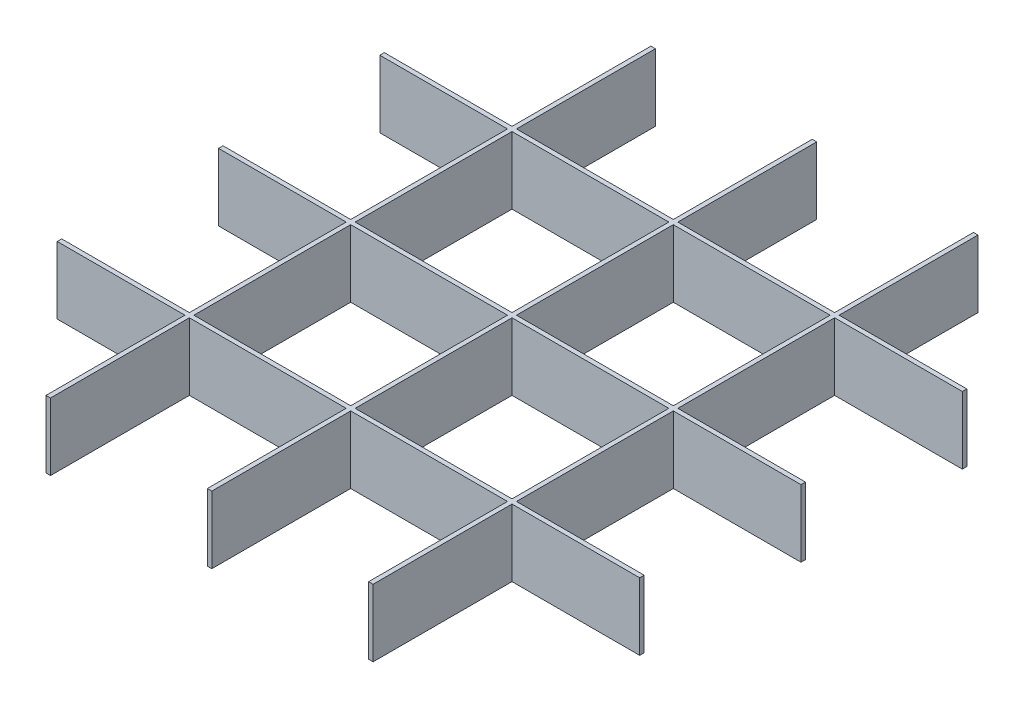
SolidWorks part; units mm, degrees
ref_plane "前视基准面" through (0, 0, 0) normal (0, 0, 1) x (1, 0, 0)
ref_plane "上视基准面" through (0, 0, 0) normal (0, 1, 0) x (1, 0, 0)
ref_plane "右视基准面" through (0, 0, 0) normal (1, 0, 0) x (0, 0, -1)
other "Configuration Table"
sketch "草图1" plane through (0, 0, 0) normal (0, 1, 0) x (1, 0, 0)
  line L0 (-130, 0) -> (130, 0) construction
  line L1 (130, -135) -> (-130, -135) construction
  line L2 (130, -135) -> (130, 135) construction
  line L3 (130, 135) -> (-130, 135) construction
  line L4 (-130, -135) -> (-130, 135) construction
  line L5 (130, -135) -> (-130, 135) construction
  line L6 (130, 135) -> (-130, -135) construction
  line L7 (0, 135) -> (0, -135) construction
  line L8 (-71, 73) -> (-1, 73)
  line L9 (-130, 73) -> (-73, 73)
  line L10 (-130, 73) -> (-130, 71)
  line L11 (-130, 71) -> (-73, 71)
  line L12 (130, 73) -> (130, 71)
  line L13 (-130, 1) -> (-73, 1)
  line L14 (-130, 1) -> (-130, -1)
  line L15 (-130, -1) -> (-73, -1)
  line L16 (130, 1) -> (130, -1)
  line L17 (-130, -71) -> (-73, -71)
  line L18 (-130, -71) -> (-130, -73)
  line L19 (-130, -73) -> (-73, -73)
  line L20 (130, -71) -> (130, -73)
  line L21 (-73, 135) -> (-71, 135)
  line L22 (-73, 135) -> (-73, 73)
  line L23 (-73, -135) -> (-71, -135)
  line L24 (-71, 135) -> (-71, 73)
  line L25 (-1, 135) -> (1, 135)
  line L26 (-1, 135) -> (-1, 73)
  line L27 (-1, -135) -> (1, -135)
  line L28 (1, 135) -> (1, 73)
  line L29 (71, 135) -> (73, 135)
  line L30 (71, 135) -> (71, 73)
  line L31 (71, -135) -> (73, -135)
  line L32 (73, 135) -> (73, 73)
  line L33 (-71, 71) -> (-1, 71)
  line L34 (-71, 71) -> (-71, 1)
  line L35 (-73, 71) -> (-73, 1)
  line L36 (-71, 1) -> (-1, 1)
  line L37 (-71, -1) -> (-71, -71)
  line L38 (-73, -1) -> (-73, -71)
  line L39 (-71, -1) -> (-1, -1)
  line L40 (-71, -71) -> (-1, -71)
  line L41 (-71, -73) -> (-1, -73)
  line L42 (-73, -73) -> (-73, -135)
  line L43 (-71, -73) -> (-71, -135)
  line L44 (-1, -73) -> (-1, -135)
  line L45 (1, -71) -> (71, -71)
  line L46 (1, -73) -> (71, -73)
  line L47 (1, -73) -> (1, -135)
  line L48 (71, -73) -> (71, -135)
  line L49 (73, -73) -> (73, -135)
  line L50 (73, -73) -> (130, -73)
  line L51 (73, -71) -> (130, -71)
  line L52 (1, 71) -> (71, 71)
  line L53 (1, 73) -> (71, 73)
  line L54 (-1, 71) -> (-1, 1)
  line L55 (1, 71) -> (1, 1)
  line L56 (73, 73) -> (130, 73)
  line L57 (71, 71) -> (71, 1)
  line L58 (73, 71) -> (73, 1)
  line L59 (73, 71) -> (130, 71)
  line L60 (73, 1) -> (130, 1)
  line L61 (1, 1) -> (71, 1)
  line L62 (-1, -1) -> (-1, -71)
  line L63 (1, -1) -> (1, -71)
  line L64 (71, -1) -> (71, -71)
  line L65 (1, -1) -> (71, -1)
  line L66 (73, -1) -> (130, -1)
  line L67 (73, -1) -> (73, -71)
  point P0 (0, 0)
  dimension "D1" = 260
  dimension "D2" = 270
  dimension "D3" = 2
  dimension "D4" = 70
extrude "凸台-拉伸2" add sketch "草图1" along normal blind 30
